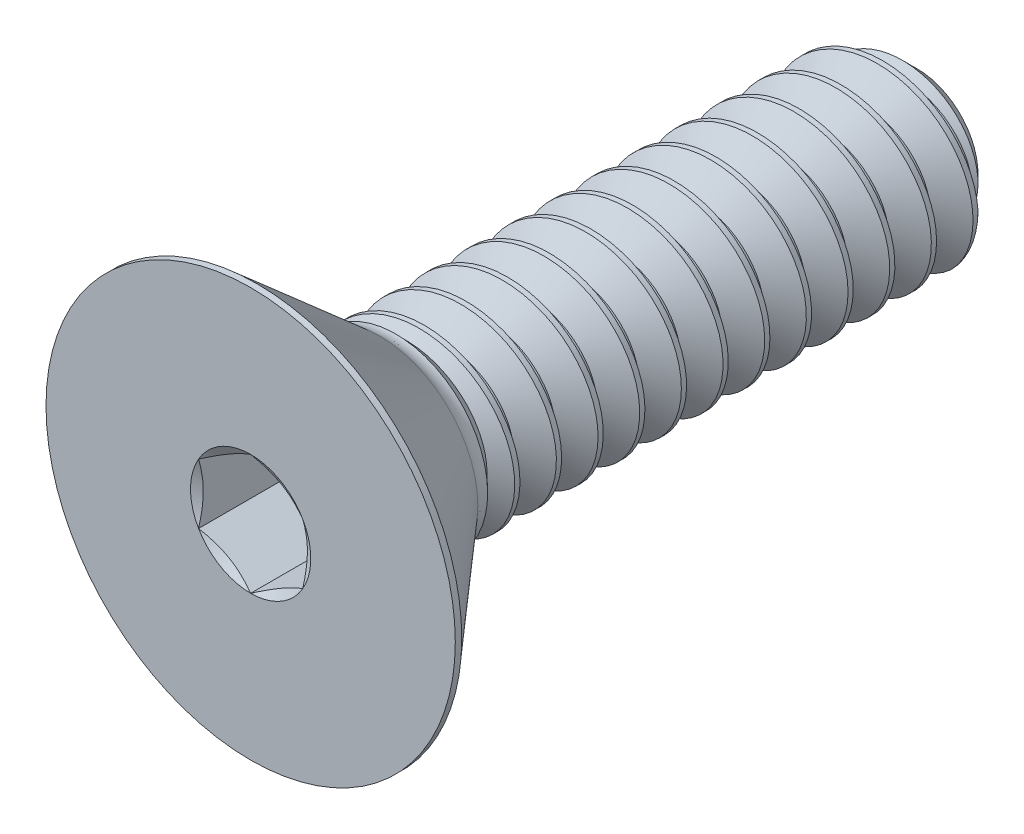
SolidWorks part; units mm, degrees
ref_plane "Front" through (0, 0, 0) normal (0, 0, 1) x (1, 0, 0)
ref_plane "Top" through (0, 0, 0) normal (0, 1, 0) x (1, 0, 0)
ref_plane "Right" through (0, 0, 0) normal (1, 0, 0) x (0, 0, -1)
sketch "Sketch1" plane through (0, 0, 0) normal (1, 0, 0) x (0, 0, -1)
  line L0 (0, 3.8989) -> (0.1232, 3.8989) construction
  line L1 (0.1232, 3.8989) -> (2.4638, 1.8642) construction
  line L2 (0, 1.7526) -> (12.7, 1.7526)
  line L3 (12.7, 1.7526) -> (12.7, 0)
  line L4 (12.7, 0) -> (0, 0)
  line L5 (0, 0) -> (0, 3.8989) construction
  line L6 (0, 3.8989) -> (0, -3.8989) construction
  line L7 (12.7, 1.7526) -> (12.7, -1.7526) construction
  line L8 (0, -3.8989) -> (0.1232, -3.8989) construction
  line L9 (0.1232, -3.8989) -> (2.4638, -1.8642) construction
  line L11 (0, 1.7526) -> (0, 0)
  line L12 (2.7624, 1.7526) -> (2.7624, 0) construction
  line L13 (-12.7, 0) -> (-12.7, 1.7526) construction
  arc A1 (2.4638, 1.8642) -> (2.7624, 1.7526) centre (2.7624, 2.2077) ccw construction
  dimension "D1" = 0.1232
  dimension "Head Ht" = 2.4638
  dimension "Head Dia" = 7.7978
  dimension "Dia" = 3.5052
  dimension "Lg" = 12.7
  dimension "Head Angle" = 82
  dimension "Min Thread" = 25.4
revolve "Revolve1" add sketch "Sketch1" angle 360 mid plane about L4
sketch "Sketch3" plane through (0, 0, -12.7) normal (0, 0, -1) x (-1, 0, 0)
  circle A0 centre (0, 0) radius 1.7526
curve "Helix/Spiral1" pitch 0.7937 height 12.7 radius 1.7526 centre (0, 0, -12.7) axis (0, 0, 1) start towards (0, 1, 0)
sketch "Sketch2" plane through (0, 0, 0) normal (1, 0, 0) x (0, 0, -1)
  line L0 (12.7, 1.7526) -> (13.3945, 1.7526)
  line L1 (13.3945, 1.7526) -> (13.0969, 1.237)
  line L2 (13.0969, 1.237) -> (12.9977, 1.237)
  line L3 (12.9977, 1.237) -> (12.7, 1.7526)
  line L4 (12.8488, 1.4948) -> (13.2457, 1.4948) construction
  dimension "D1" = 60
  dimension "D2" = 0.0992
  dimension "D3" = 0.3969
ref_plane "Plane2" through (0, 0, 12.7) normal (0, 0, 1) x (1, 0, 0)
chamfer "Chamfer1" distance 0.5953 angle 45 1 edges at (0, 1.7526, -12.7)
sweep "Cut-Sweep1" cut profiles "Sketch2" path "Helix/Spiral1"
sketch "Sketch7" plane through (0, 0, 0) normal (1, 0, 0) x (0, 0, -1)
  line L0 (0, 3.8989) -> (0.1232, 3.8989) construction
  line L1 (0.1232, 3.8989) -> (2.4638, 1.8642) construction
  line L2 (0, 3.8989) -> (0.1232, 3.8989)
  line L3 (0.1232, 3.8989) -> (2.4638, 1.8642)
  line L4 (2.7624, 1.7526) -> (2.7624, 0) construction
  line L5 (2.7624, 1.7526) -> (2.7624, 0)
  line L7 (0, 0) -> (0, 3.8989) construction
  line L8 (0, 0) -> (0, 3.8989)
  line L9 (0, 0) -> (2.7624, 0)
  line L10 (5.7417, 0) -> (-5.7417, 0) construction
  arc A0 (2.4638, 1.8642) -> (2.7624, 1.7526) centre (2.7624, 2.2077) ccw construction
  arc A1 (2.4638, 1.8642) -> (2.7624, 1.7526) centre (2.7624, 2.2077) ccw
revolve "Revolve2" add sketch "Sketch7" angle 360 mid plane about L9
ref_plane "Plane1" through (0, 0, -2.7624) normal (0, 0, 1) x (1, 0, 0)
sketch "Sketch8" plane through (0, 0, -2.7624) normal (0, 0, 1) x (1, 0, 0)
  circle A0 centre (0, 0) radius 1.7526
extrude "Boss-Extrude1" add sketch "Sketch8" against normal through all draft 46
sketch "Sketch5" plane through (0, 0, 0) normal (0, 0, 1) x (1, 0, 0)
  line L0 (0, 0) -> (-1.1457, 0) construction
  line L1 (0, 0) -> (-2.7496, 1.5875) construction
  line L2 (0, 0) -> (-2.7496, -1.5875) construction
  line L6 (0, 1.1457) -> (0, 0.9449) construction
  line L7 (0, 0.9449) -> (0, 0.7441) construction
  line L9 (0, 1.1457) -> (-0.9922, 0.5728)
  line L10 (-0.9922, 0.5728) -> (-0.9922, -0.5728)
  line L11 (-0.9922, -0.5728) -> (0, -1.1457)
  line L12 (0, -1.1457) -> (0.9922, -0.5728)
  line L13 (0.9922, -0.5728) -> (0.9922, 0.5728)
  line L14 (0.9922, 0.5728) -> (0, 1.1457)
  circle A0 centre (0, 0) radius 1.1457 construction
  circle A1 centre (0, 0) radius 0.9449 construction
  circle A2 centre (0, 0) radius 0.7441 construction
  circle A3 centre (0, 0) radius 0.9922 construction
  dimension "D3" = 1.4883
  dimension "Hex" = 1.9844
  dimension "D4" = 30
  dimension "D5" = 30
extrude "Cut-Extrude2" cut sketch "Sketch5" against normal blind 1.7247
sketch "Sketch6" plane through (0, 0, 0) normal (0, 0, 1) x (1, 0, 0)
  circle A0 centre (0, 0) radius 1.1457
extrude "Cut-Extrude3" cut sketch "Sketch6" against normal blind 1.7247 draft 60
sketch "Sketch9" [suppressed] plane through (0, 0, -3.6076) normal (0, 0, 1) x (1, 0, 0)
  circle A1 centre (0, 0) radius 2.413
  circle A2 centre (0, 0) radius 2.413
  point P0 (0, 2.413)
  dimension "D1" = 0
extrude "Boss-Extrude2" [suppressed] add sketch "Sketch9" against normal up to surface (15.4424 mm away) up to plane "Plane2"
sketch "Sketch10" plane through (0, 0, 0) normal (1, 0, 0) x (0, 0, -1)
  line L0 (12.7, 1.7526) -> (12.7, -1.7526) construction
  point P0 (11.5094, -1.7526)
  dimension "D1" = 1.1906
equation "\"D3@Helix/Spiral1\" = \"Lg@Sketch1\""
equation "\"D2@Sketch2\" = \"D4@Helix/Spiral1\" * .125"
equation "\"D3@Sketch2\" = \"D4@Helix/Spiral1\" * .5"
equation "\"D1@Chamfer1\" = \"D4@Helix/Spiral1\" * .75"
equation "\"D1@Cut-Extrude2\" = \"Head Ht@Sketch1\" * .7"
equation "\"D1@Sketch1\" = \"Head Ht@Sketch1\" * .05"
equation "\"D1@Sketch10\" = \"D4@Helix/Spiral1\" * 1.5"
equation "\"D1@Cut-Extrude3\" = \"D1@Cut-Extrude2\""
equation "\"D3@Sketch5\" = \"Hex@Sketch5\" * .75"
